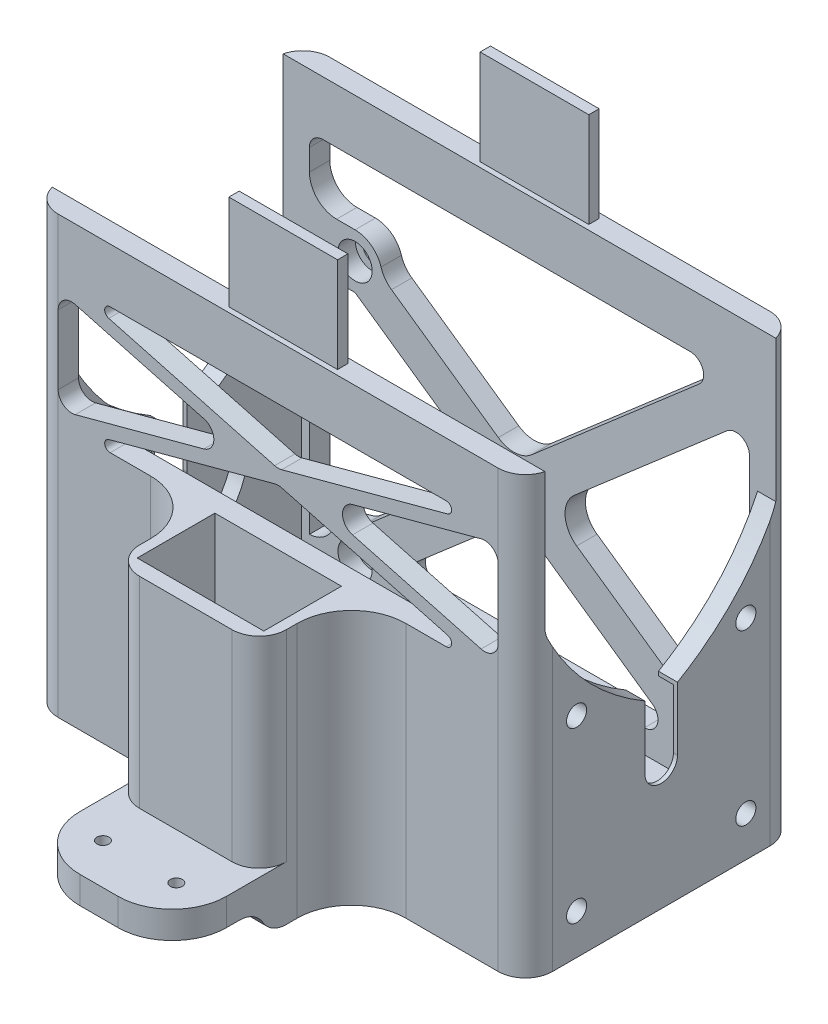
SolidWorks part; units mm, degrees
ref_plane "Plan de face" through (0, 0, 0) normal (0, 0, 1) x (1, 0, 0)
ref_plane "Plan de dessus" through (0, 0, 0) normal (0, 1, 0) x (1, 0, 0)
ref_plane "Plan de droite" through (0, 0, 0) normal (1, 0, 0) x (0, 0, -1)
sketch "Esquisse1" plane through (0, 0, 0) normal (1, 0, 0) x (0, 0, -1)
  line L2 (-15.8423, 13.6674) -> (-15.8423, -28.8326)
  line L3 (-15.8423, -28.8326) -> (26.6577, -28.8326)
  line L4 (26.6577, 13.6674) -> (26.6577, -28.8326)
  line L7 (-19.5923, -31.5826) -> (30.4077, -31.5826)
  line L10 (-19.5923, 14.3416) -> (-19.5923, -31.5826)
  line L11 (30.4077, 13.6674) -> (30.4077, -31.5826)
  line L12 (-15.8423, 13.6674) -> (-15.8423, 48.6674)
  line L13 (-19.5923, 14.3416) -> (-19.5923, 48.6674)
  line L14 (-19.5923, 48.6674) -> (-15.8423, 48.6674)
  line L18 (5.4077, -28.8326) -> (5.4077, -31.5826) construction
  line L25 (26.6577, 13.6674) -> (26.6577, 48.6674)
  line L26 (26.6577, 48.6674) -> (30.4077, 48.6674)
  line L27 (30.4077, 48.6674) -> (30.4077, 13.6674)
  dimension "D1" = 42.5
  dimension "D2" = 42.5
  dimension "D3" = 35
  dimension "D4" = 2.75
extrude "Boss.-Extru.1" add sketch "Esquisse1" along normal blind 84
sketch "Esquisse6" plane through (0, 0, 19.5923) normal (0, 0, 1) x (1, 0, 0)
  line L0 (38.608, -31.5826) -> (48.8838, -31.5826) construction
  line L1 (84, -31.5826) -> (0, -31.5826) construction
  line L3 (28.5, 15.4174) -> (55.5, 15.4174)
  line L4 (28.5, 15.4174) -> (28.5, -31.5826)
  line L5 (28.5, -31.5826) -> (55.5, -31.5826)
  line L6 (55.5, 15.4174) -> (55.5, -31.5826)
  dimension "D3" = 27
  dimension "D4" = 47
  dimension "0" = 0
extrude "Boss.-Extru.3" add sketch "Esquisse6" along normal blind 17
sketch "Esquisse7" plane through (0, 15.4174, 0) normal (0, 1, 0) x (1, 0, 0)
  line L0 (55.5, -19.5923) -> (28.5, -19.5923) construction
  line L2 (30.35, -19.5923) -> (53.65, -19.5923)
  line L3 (30.35, -19.5923) -> (30.35, -33.8923)
  line L4 (30.35, -33.8923) -> (53.65, -33.8923)
  line L5 (53.65, -19.5923) -> (53.65, -33.8923)
  line L6 (55.5, -36.5923) -> (55.5, -19.5923) construction
  dimension "D1" = 14.3
  dimension "D2" = 23.3
  dimension "D3" = 1.85
  dimension "D4" = 0
extrude "Enlèv. mat.-Extru.4" cut sketch "Esquisse7" against normal blind 43.3
sketch "Esquisse8" plane through (84, 0, 0) normal (1, 0, 0) x (0, 0, -1)
  line L3 (-19.5923, -31.5826) -> (30.4077, -31.5826)
  line L4 (-10.1673, 6.9924) -> (20.9827, -24.1576) construction
  line L5 (-10.1673, -23.1576) -> (20.9827, -23.1576) construction
  line L6 (-10.1673, -24.1576) -> (-10.1673, 6.9924) construction
  line L7 (-10.1673, 7.9924) -> (-4.5822, 7.9924) construction
  line L8 (20.9827, -23.1576) -> (20.9827, 7.9924) construction
  line L9 (-10.1673, -24.1576) -> (20.9827, 6.9924) construction
  line L10 (-19.5923, 13.6674) -> (-19.5923, -31.5826)
  line L11 (30.4077, 13.6674) -> (30.4077, -31.5826)
  line L12 (-15.8423, -28.8326) -> (26.6577, -28.8326) construction
  line L13 (5.4077, -28.8326) -> (5.4077, -7.5826) construction
  line L14 (2.4077, -7.5826) -> (2.4077, 3.0424)
  line L15 (8.4077, -7.5826) -> (8.4077, 3.0424)
  line L19 (-19.5923, 28.6674) -> (-19.5923, 13.6674)
  line L23 (5.4077, 7.9924) -> (5.4077, 6.9924) construction
  line L24 (2.4077, -7.5826) -> (2.4077, -8.5826)
  line L25 (8.4077, -7.5826) -> (8.4077, -8.5826)
  line L30 (-19.5923, 48.6674) -> (-19.5923, 28.6674)
  line L31 (2.4077, 7.9924) -> (20.9827, 7.9924) construction
  line L32 (30.4077, 33.6674) -> (30.4077, 13.6674)
  line L33 (-19.5923, 48.6674) -> (-15.8423, 48.6674)
  line L34 (-15.8423, 48.6674) -> (-15.8423, 22.6208)
  line L36 (26.6577, 33.6674) -> (26.6577, 22.6208)
  line L39 (26.6577, 48.6674) -> (30.4077, 48.6674)
  line L40 (26.6577, 48.6674) -> (26.6577, 33.6674)
  line L42 (30.4077, 48.6674) -> (30.4077, 33.6674)
  arc A0 (2.4077, -8.5826) -> (8.4077, -8.5826) centre (5.4077, -8.5826) ccw
  circle A1 centre (-10.1673, 6.9924) radius 1.85
  circle A2 centre (20.9827, 6.9924) radius 1.85
  circle A3 centre (20.9827, -24.1576) radius 1.85
  circle A4 centre (-10.1673, -24.1576) radius 1.85
  spline S0 degree 3 poles (-15.8423, 22.6208) (-11.9279, 14.4292) (-5.8446, 7.9031) (2.4077, 3.0424) knots 0.293072 0.293072 0.293072 0.293072 1 1 1 1
  spline S1 degree 3 poles (26.6577, 22.6208) (22.7433, 14.4292) (16.66, 7.9031) (8.4077, 3.0424) knots 0.293072 0.293072 0.293072 0.293072 1 1 1 1
  point P18 (5.4077, -8.5826)
  dimension "D2" = 1
  dimension "D1" = 21.25
extrude "Boss.-Extru.4" add sketch "Esquisse8" along normal blind 3.5
sketch "Esquisse12" plane through (84, 0, 0) normal (-1, 0, 0) x (0, 0, 1)
  circle A0 centre (-5.4077, -8.5826) radius 11.275
  dimension "D1" = 22.55
extrude "Enlèv. mat.-Extru.7" cut sketch "Esquisse12" against normal blind 2.75
ref_plane "Plan1" through (42, 0, 0) normal (-1, 0, 0) x (0, 0, 1)
mirror "Symétrie1" about plane through (42, 0, 0) normal (-1, 0, 0) of "Boss.-Extru.4", "Enlèv. mat.-Extru.7"
sketch "Esquisse13" plane through (0, 0, 36.5923) normal (0, 0, 1) x (1, 0, 0)
  line L0 (28.5, 15.4174) -> (28.5, -31.5826) construction
  line L1 (55.5, -31.5826) -> (28.5, -31.5826)
  line L2 (55.5, -31.5826) -> (55.5, -21.5826)
  line L3 (55.5, -21.5826) -> (28.5, -21.5826)
  line L4 (28.5, -31.5826) -> (28.5, -21.5826)
  dimension "10" = 10
extrude "Boss.-Extru.5" add sketch "Esquisse13" along normal blind 16
sketch "Esquisse15" plane through (0, -31.5826, 0) normal (0, -1, 0) x (1, 0, 0)
  line L0 (55.5, 52.5923) -> (55.5, 19.5923) construction
  line L1 (28.5, 59.0923) -> (55.5, 59.0923)
  line L2 (28.5, 59.0923) -> (28.5, 36.5923)
  line L3 (28.5, 36.5923) -> (55.5, 36.5923)
  line L4 (55.5, 59.0923) -> (55.5, 36.5923)
  dimension "D1" = 22.5
extrude "Enlèv. mat.-Extru.9" cut sketch "Esquisse15" against normal blind 5
sketch "Esquisse14" plane through (0, -31.5826, 0) normal (0, -1, 0) x (1, 0, 0)
  line L0 (42, 44.0923) -> (42, 45.0923) construction
  line L1 (35.25, 45.0923) -> (48.75, 45.0923) construction
  line L4 (28.5, 36.5923) -> (55.5, 36.5923) construction
  line L5 (55.5, 36.5923) -> (55.5, 19.5923) construction
  circle A0 centre (35.25, 45.0923) radius 1.11
  circle A1 centre (48.75, 45.0923) radius 1.11
  point P3 (42, 44.0923)
  point P14 (42, 44.0923)
  dimension "D1" = 13.5
  dimension "D2" = 1
extrude "Enlèv. mat.-Extru.8" cut sketch "Esquisse14" against normal blind 15
fillet "Congé6" radius 5 1 edges at (42, -31.5826, 36.5923)
fillet "Congé7" radius 5 1 edges at (42, -26.5826, 36.5923)
fillet "Congé1" radius 10 2 edges at (28.5, -24.0826, 52.5923) (55.5, -24.0826, 52.5923)
fillet "Congé3" radius 10 2 edges at (55.5, -8.0826, 19.5923) (28.5, -8.0826, 19.5923)
fillet "Congé4" radius 5 2 edges at (-3.5, 8.5424, 19.5923) (87.5, 8.5424, 19.5923)
fillet "Congé8" radius 5 2 edges at (55.5, -3.0826, 36.5923) (28.5, -3.0826, 36.5923)
sketch "Esquisse20" plane through (0, 0, -30.4077) normal (0, 0, -1) x (-1, 0, 0)
  line L8 (-76.1021, -25.5192) -> (-9.9016, -25.5192) construction
  line L9 (-9.9016, -25.5192) -> (-9.9016, 22.2308) construction
  line L10 (-9.9016, 22.2308) -> (-76.1021, -25.5192) construction
  circle A4 centre (-9.9016, 22.2308) radius 1.7
  circle A5 centre (-9.9016, -25.5192) radius 1.7
  circle A6 centre (-76.1021, -25.5192) radius 1.7
  dimension "D3" = 3.4
  dimension "D1" = 3.4
  dimension "D2" = 3.4
sketch "Esquisse22" plane through (0, -28.8326, 0) normal (0, 1, 0) x (1, 0, 0)
  line L1 (0, 26.6577) -> (84, 26.6577)
  line L2 (0, 26.6577) -> (0, -15.8423)
  line L3 (0, -15.8423) -> (84, -15.8423)
  line L4 (84, 26.6577) -> (84, -15.8423)
extrude "Enlèv. mat.-Extru.12" cut sketch "Esquisse22" against normal blind 1
fillet "Congé12" radius 5 2 edges at (87.5, 8.5424, -30.4077) (-3.5, 8.5424, -30.4077)
extrude "Enlèv. mat.-Extru.13" cut sketch "Esquisse20" against normal blind 10
sketch "Esquisse23" plane through (0, 0, -26.6577) normal (0, 0, 1) x (1, 0, 0)
  circle A0 centre (9.9016, 22.2308) radius 3.15
  circle A1 centre (9.9016, -25.5192) radius 3.15
  circle A2 centre (76.1021, -25.5192) radius 3.15
  dimension "D1" = 6.3
  dimension "D2" = 6.3
  dimension "D3" = 6.3
extrude "Enlèv. mat.-Extru.14" cut sketch "Esquisse23" against normal blind 3.2
sketch "Esquisse24" plane through (0, 48.6674, 0) normal (0, 1, 0) x (1, 0, 0)
  line L1 (32, 29.4827) -> (52, 29.4827)
  line L2 (32, 29.4827) -> (32, 27.5827)
  line L3 (32, 27.5827) -> (52, 27.5827)
  line L4 (52, 29.4827) -> (52, 27.5827)
  line L8 (84, 26.6577) -> (0, 26.6577) construction
  line L9 (0, 5.4077) -> (84, 5.4077) construction
  line L10 (0, 26.6577) -> (0, -15.8423) construction
  line L11 (84, 16.6827) -> (84, -5.8673) construction
  line L12 (32, -16.7673) -> (52, -16.7673)
  line L13 (52, -18.6673) -> (52, -16.7673)
  line L14 (32, -18.6673) -> (52, -18.6673)
  line L15 (32, -18.6673) -> (32, -16.7673)
  line L16 (0, 8.4077) -> (0, 26.6577) construction
  dimension "D1" = 20
  dimension "D2" = 32
  dimension "D3" = 1.9
  dimension "D4" = 0.925
extrude "Boss.-Extru.6" add sketch "Esquisse24" along normal blind 17.5
fillet "Congé13" radius 5 2 edges at (-1.6706, 22.6208, 15.8423) (85.6706, 22.6208, 15.8423)
sketch "Esquisse25" plane through (0, 0, -30.4077) normal (0, 0, -1) x (-1, 0, 0)
  line L0 (-1.5, -31.5826) -> (-1.5, 48.6674) construction
  line L2 (-1.5, 36.7939) -> (-1.5, 27.2308)
  line L3 (-1.5, -25.5192) -> (-4.9016, -25.5192)
  line L4 (-82.5, 33.0041) -> (-82.5, -25.5192)
  line L5 (-82.5, 48.6674) -> (-82.5, -31.5826) construction
  line L6 (-9.9016, 27.2308) -> (-1.5, 27.2308)
  line L7 (-9.9016, 17.2308) -> (-1.5, 17.2308)
  line L8 (-1.5, 17.2308) -> (-1.5, -25.5192)
  line L9 (-81.1021, -25.5192) -> (-82.5, -25.5192)
  line L10 (-14.9016, -25.5192) -> (-71.1021, -25.5192)
  line L11 (-76.1021, 36.7939) -> (-39.4633, 5.0739)
  line L12 (-14.9016, -25.5192) -> (-39.9979, -3.7921)
  line L13 (-71.1021, -25.5192) -> (-39.9979, -3.7921)
  line L14 (-14.9016, 22.2308) -> (-39.4633, 5.0739)
  line L15 (-34.0342, 0.3736) -> (-9.9016, -20.5192)
  line L16 (-45.427, 0.9081) -> (-82.5, 33.0041)
  line L17 (-34.0342, 0.3736) -> (-9.9016, 17.2308)
  line L18 (-45.427, 0.9081) -> (-76.1021, -20.5192)
  line L19 (-67.3721, 48.6674) -> (-67.3721, 38.6674) construction
  line L20 (-82.5, 48.6674) -> (-1.5, 48.6674) construction
  line L21 (-78.2662, 38.6674) -> (-1.5, 38.6674)
  line L22 (-1.5, 36.7939) -> (-1.5, 38.6674)
  line L24 (-76.1021, 36.7939) -> (-78.2662, 38.6674)
  arc A0 (-9.9016, 27.2308) -> (-14.9016, 22.2308) centre (-9.9016, 22.2308) ccw
  arc A1 (-76.1021, -20.5192) -> (-81.1021, -25.5192) centre (-76.1021, -25.5192) ccw
  arc A2 (-4.9016, -25.5192) -> (-9.9016, -20.5192) centre (-9.9016, -25.5192) ccw
  dimension "D1" = 10
  dimension "D2" = 10
  dimension "D3" = 10
  dimension "D4" = 10
  dimension "D5" = 180
extrude "Enlèv. mat.-Extru.15" cut sketch "Esquisse25" against normal blind 10
fillet "Congé14" radius 5 6 edges at (1.5, 27.2308, -28.5327) (81.1021, -25.5192, -28.5327) (4.9016, -25.5192, -28.5327) (9.9016, -20.5192, -28.5327) (76.1021, -20.5192, -28.5327) (14.9016, 22.2308, -28.5327)
fillet "Congé15" radius 5 4 edges at (39.9979, -3.7921, -28.5327) (34.0342, 0.3736, -28.5327) (39.4633, 5.0739, -28.5327) (45.427, 0.9081, -28.5327)
fillet "Congé16" radius 2.5 5 edges at (71.1021, -25.5192, -28.5327) (14.9016, -25.5192, -28.5327) (82.5, 33.0041, -28.5327) (1.5, 38.6674, -28.5327) (78.2662, 38.6674, -28.5327)
fillet "Congé17" radius 2.5 1 edges at (82.5, -25.5192, -28.5327)
sketch "Esquisse26" plane through (0, 0, 19.5923) normal (0, 0, 1) x (1, 0, 0)
  line L5 (3.5, 38.6674) -> (80.5, 38.6674)
  line L6 (1.5, 36.6674) -> (1.5, 17.4174)
  line L7 (3.5, 15.4174) -> (80.5, 15.4174)
  line L8 (82.5, 36.6674) -> (82.5, 17.4174)
  line L10 (82.5, 48.6674) -> (1.5, 48.6674) construction
  line L11 (3.5, 38.6674) -> (42, 28.3114)
  line L12 (1.5, 36.6674) -> (37.2824, 27.0424)
  line L13 (50.5, 15.4174) -> (33.5, 15.4174) construction
  line L14 (80.5, 38.6674) -> (42, 28.3114)
  line L15 (3.5, 15.4174) -> (42, 25.7734)
  line L16 (37.2824, 27.0424) -> (1.5, 17.4174)
  line L17 (46.7176, 27.0424) -> (82.5, 17.4174)
  line L18 (46.7176, 27.0424) -> (82.5, 36.6674)
  line L19 (42, 25.7734) -> (80.5, 15.4174)
  dimension "D1" = 10
  dimension "D2" = 2
  dimension "D3" = 2
  dimension "D4" = 2
  dimension "D5" = 2
  dimension "D6" = 0
  dimension "D7" = 2
  dimension "D8" = 2
  dimension "D9" = 2
  dimension "D10" = 2
extrude "Enlèv. mat.-Extru.17" cut sketch "Esquisse26" against normal blind 10
fillet "Congé18" radius 2.5 8 edges at (82.5, 17.4174, 17.7173) (82.5, 36.6674, 17.7173) (1.5, 17.4174, 17.7173) (1.5, 36.6674, 17.7173) (42, 25.7734, 17.7173) (37.2824, 27.0424, 17.7173) (46.7176, 27.0424, 17.7173) (42, 28.3114, 17.7173)
fillet "Congé19" radius 1 4 edges at (80.5, 15.4174, 17.7173) (3.5, 15.4174, 17.7173) (3.5, 38.6674, 17.7173) (80.5, 38.6674, 17.7173)
